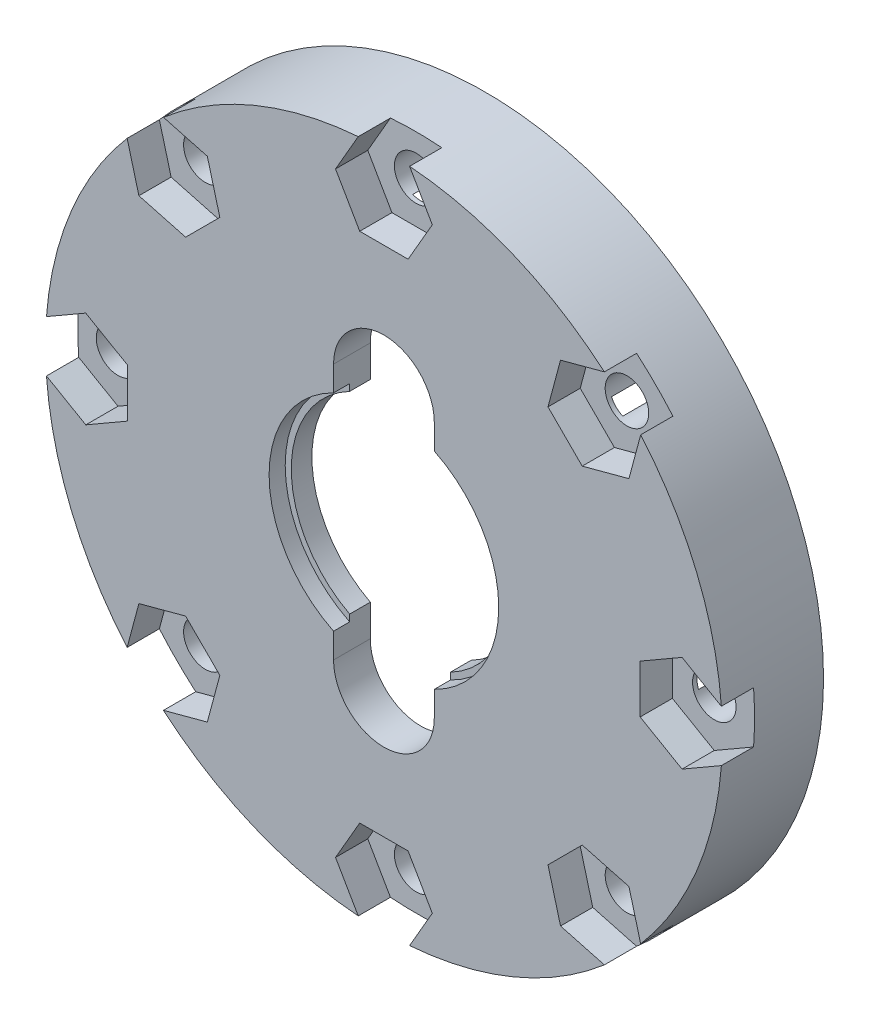
SolidWorks part; units mm, degrees
ref_plane "Front Plane" through (0, 0, 0) normal (0, 0, 1) x (1, 0, 0)
ref_plane "Top Plane" through (0, 0, 0) normal (0, 1, 0) x (1, 0, 0)
ref_plane "Right Plane" through (0, 0, 0) normal (1, 0, 0) x (0, 0, -1)
ref_axis "Z" through (0, 0, -6.594) along (0, 0, 1)
sketch "Sketch3" plane through (0, 0, 0) normal (0, 0, 1) x (1, 0, 0)
  line L0 (-3.125, -6.4031) -> (-3.125, -7.9497)
  line L1 (-3.125, -7.9497) -> (3.125, -7.9497)
  line L2 (3.125, -7.9497) -> (3.125, -6.4031)
  line L3 (3.125, 6.4031) -> (3.125, 7.9494)
  line L4 (3.125, 7.9494) -> (-3.125, 7.9494)
  line L5 (-3.125, 7.9494) -> (-3.125, 6.4031)
  line L132 (3.05, 6.3548) -> (3.05, 6.3561) construction
  line L133 (-3.05, 6.3561) -> (-3.05, 6.3548) construction
  line L134 (3.05, -6.3561) -> (3.05, -6.355) construction
  line L135 (-3.05, -6.355) -> (-3.05, -6.3561) construction
  line L198 (3.05, 6.3548) -> (3.05, 7.8744)
  line L199 (3.05, 7.8744) -> (-3.05, 7.8744)
  line L200 (-3.05, 7.8744) -> (-3.05, 6.3548)
  line L201 (-3.05, 6.3548) -> (-3.4914, 6.1247)
  line L202 (-3.4914, 6.1247) -> (-3.9416, 5.8451)
  line L203 (-3.9416, 5.8451) -> (-4.3696, 5.5325)
  line L204 (-4.3696, 5.5325) -> (-4.7729, 5.1886)
  line L205 (-4.7729, 5.1886) -> (-5.1492, 4.8154)
  line L206 (-5.1492, 4.8154) -> (-5.4964, 4.4149)
  line L207 (-5.4964, 4.4149) -> (-5.8125, 3.9896)
  line L208 (-5.8125, 3.9896) -> (-6.0958, 3.5417)
  line L209 (-6.0958, 3.5417) -> (-6.3446, 3.0737)
  line L210 (-6.3446, 3.0737) -> (-6.5576, 2.5884)
  line L211 (-6.5576, 2.5884) -> (-6.7335, 2.0885)
  line L212 (-6.7335, 2.0885) -> (-6.8714, 1.5768)
  line L213 (-6.8714, 1.5768) -> (-6.9705, 1.0561)
  line L214 (-6.9705, 1.0561) -> (-7.0301, 0.5295)
  line L215 (-7.0301, 0.5295) -> (-7.05, -0.0001)
  line L216 (-7.05, -0.0001) -> (-7.0301, -0.5297)
  line L217 (-7.0301, -0.5297) -> (-6.9705, -1.0563)
  line L218 (-6.9705, -1.0563) -> (-6.8714, -1.577)
  line L219 (-6.8714, -1.577) -> (-6.7335, -2.0887)
  line L220 (-6.7335, -2.0887) -> (-6.5576, -2.5887)
  line L221 (-6.5576, -2.5887) -> (-6.3446, -3.074)
  line L222 (-6.3446, -3.074) -> (-6.0958, -3.5419)
  line L223 (-6.0958, -3.5419) -> (-5.8125, -3.9898)
  line L224 (-5.8125, -3.9898) -> (-5.4964, -4.4152)
  line L225 (-5.4964, -4.4152) -> (-5.1492, -4.8156)
  line L226 (-5.1492, -4.8156) -> (-4.7729, -5.1888)
  line L227 (-4.7729, -5.1888) -> (-4.3696, -5.5327)
  line L228 (-4.3696, -5.5327) -> (-3.9416, -5.8453)
  line L229 (-3.9416, -5.8453) -> (-3.4914, -6.1249)
  line L230 (-3.4914, -6.1249) -> (-3.05, -6.355)
  line L231 (-3.05, -6.355) -> (-3.05, -7.8747)
  line L232 (-3.05, -7.8747) -> (3.05, -7.8747)
  line L233 (3.05, -7.8747) -> (3.05, -6.355)
  line L234 (3.05, -6.355) -> (3.4914, -6.1249)
  line L235 (3.4914, -6.1249) -> (3.9417, -5.8453)
  line L236 (3.9417, -5.8453) -> (4.3696, -5.5327)
  line L237 (4.3696, -5.5327) -> (4.7729, -5.1888)
  line L238 (4.7729, -5.1888) -> (5.1492, -4.8156)
  line L239 (5.1492, -4.8156) -> (5.4964, -4.4152)
  line L240 (5.4964, -4.4152) -> (5.8125, -3.9898)
  line L241 (5.8125, -3.9898) -> (6.0958, -3.5419)
  line L242 (6.0958, -3.5419) -> (6.3447, -3.074)
  line L243 (6.3447, -3.074) -> (6.5576, -2.5887)
  line L244 (6.5576, -2.5887) -> (6.7336, -2.0887)
  line L245 (6.7336, -2.0887) -> (6.8714, -1.577)
  line L246 (6.8714, -1.577) -> (6.9705, -1.0563)
  line L247 (6.9705, -1.0563) -> (7.0301, -0.5297)
  line L248 (7.0301, -0.5297) -> (7.05, -0.0001)
  line L249 (7.05, -0.0001) -> (7.0301, 0.5295)
  line L250 (7.0301, 0.5295) -> (6.9705, 1.0561)
  line L251 (6.9705, 1.0561) -> (6.8714, 1.5768)
  line L252 (6.8714, 1.5768) -> (6.7336, 2.0885)
  line L253 (6.7336, 2.0885) -> (6.5576, 2.5884)
  line L254 (6.5576, 2.5884) -> (6.3447, 3.0737)
  line L255 (6.3447, 3.0737) -> (6.0958, 3.5417)
  line L256 (6.0958, 3.5417) -> (5.8125, 3.9896)
  line L257 (5.8125, 3.9896) -> (5.4964, 4.4149)
  line L258 (5.4964, 4.4149) -> (5.1492, 4.8154)
  line L259 (5.1492, 4.8154) -> (4.7729, 5.1886)
  line L260 (4.7729, 5.1886) -> (4.3696, 5.5325)
  line L261 (4.3696, 5.5325) -> (3.9417, 5.8451)
  line L262 (3.9417, 5.8451) -> (3.4914, 6.1247)
  line L263 (3.4914, 6.1247) -> (3.05, 6.3548)
  line L264 (3.05, 6.3561) -> (3.05, 7.8744) construction
  line L265 (3.05, 7.8744) -> (-3.05, 7.8744) construction
  line L266 (-3.05, 7.8744) -> (-3.05, 6.3561) construction
  line L297 (-3.05, -6.3561) -> (-3.05, -7.8747) construction
  line L298 (-3.05, -7.8747) -> (3.05, -7.8747) construction
  line L299 (3.05, -7.8747) -> (3.05, -6.3561) construction
  arc A1 (-3.05, 6.3561) -> (-3.05, -6.3561) centre (0, 0) ccw construction
  arc A2 (3.05, 6.3561) -> (-3.05, 6.3561) centre (0, 0) ccw construction
  arc A3 (3.05, -6.3561) -> (3.05, 6.3561) centre (0, 0) ccw construction
  arc A4 (-3.05, -6.3561) -> (3.05, -6.3561) centre (0, 0) ccw construction
  circle A5 centre (0, 0) radius 21
  arc A6 (-3.125, 6.4031) -> (-3.125, -6.4031) centre (0, 0) ccw
  arc A7 (3.125, -6.4031) -> (3.125, 6.4031) centre (0, 0) ccw
  dimension "D1" = 14.1
  dimension "D3" = 42
  dimension "D2" = 0.075
  dimension "D4" = 0.075
extrude "Boss-Extrude2" add sketch "Sketch3" against normal blind 1
sketch "Sketch4" plane through (0, 0, -1) normal (0, 0, -1) x (-1, 0, 0)
  line L39 (2.75, 6.1644) -> (2.75, 7.5744)
  line L40 (2.75, 7.5744) -> (-2.75, 7.5744)
  line L41 (-2.75, 7.5744) -> (-2.75, 6.1644)
  line L42 (-2.75, -6.1644) -> (-2.75, -7.5747)
  line L43 (-2.75, -7.5747) -> (2.75, -7.5747)
  line L44 (2.75, -7.5747) -> (2.75, -6.1644)
  circle A14 centre (0, 0) radius 21
  arc A17 (-2.75, 6.1644) -> (-2.75, -6.1644) centre (0, 0) ccw
  arc A18 (2.75, -6.1644) -> (2.75, 6.1644) centre (0, 0) ccw
  dimension "D1" = 42
extrude "Boss-Extrude3" add sketch "Sketch4" along normal blind 5.28
sketch "Sketch5" plane through (0, 0, -6.28) normal (0, 0, -1) x (-1, 0, 0)
  circle A0 centre (0, 0) radius 17.25
  dimension "D1" = 34.5
extrude "Cut-Extrude1" cut sketch "Sketch5" against normal blind 4
sketch "Sketch6" plane through (0, 0, 0) normal (0, 0, 1) x (1, 0, 0)
  line L0 (0, 0) -> (-18.5, 0) construction
  line L1 (-16.3801, 0) -> (0, 0) construction
  line L3 (-21.1, -1.5011) -> (-18.5, -3.0022)
  line L4 (-18.5, -3.0022) -> (-15.9, -1.5011)
  line L5 (-15.9, -1.5011) -> (-15.9, 1.5011)
  line L6 (-15.9, 1.5011) -> (-18.5, 3.0022)
  line L7 (-18.5, 3.0022) -> (-21.1, 1.5011)
  line L8 (-21.1, 1.5011) -> (-21.1, -1.5011)
  circle A0 centre (-18.5, 0) radius 2.6 construction
  dimension "D1" = 0
  dimension "D2" = 18.5
  dimension "D3" = 5.2
extrude "Cut-Extrude2" cut sketch "Sketch6" against normal blind 2
sketch "Sketch8" plane through (0, 0, 0) normal (0, 0, 1) x (1, 0, 0)
  line L0 (36.6653, 0) -> (49.0214, 0) construction
  line L1 (0, 0) -> (-18.5, 0) construction
  circle A0 centre (0, 0) radius 18.5 construction
  circle A1 centre (-18.5, 0) radius 1.35
  dimension "D1" = 37
  dimension "D3" = 2.7
  dimension "D2" = 0
extrude "Cut-Extrude4" cut sketch "Sketch8" against normal through all
pattern_circular "CirPattern1" count 8 over 360 about axis through (0, 0, -6.594) along (0, 0, 1) of "Cut-Extrude2", "Cut-Extrude4"
ref_plane "Plane4" through (0, 0, 0) normal (-0.7071, 0.7071, 0) x (0, 0, 1)
sketch "Sketch9" plane through (0, 0, 0) normal (0, 0, 1) x (1, 0, 0)
  line L1 (-3.125, 7.9494) -> (-3.125, 10.495) construction
  line L2 (0, 0) -> (3.8744, 0) construction
  line L4 (3.125, 7.9494) -> (3.125, -7.9494)
  line L5 (-3.125, 7.9494) -> (-3.125, -7.9494)
  arc A0 (-3.125, 7.9494) -> (3.125, 7.9494) centre (0, 7.9494) cw
  arc A1 (-3.125, -7.9494) -> (3.125, -7.9494) centre (0, -7.9494) ccw
extrude "Cut-Extrude5" cut sketch "Sketch9" against normal through all
equation "\"BearingOD\"= 32"
equation "\"BearingID\" = 25"
equation "\"BearingHeight\"= 4"
equation "\"RetainingRingThickness\" = 1.30"
equation "\"BearingBaseDistance\"= 17.2 - 2*\"BearingHeight\"  - \"RetainingRingThickness\"*2"
equation "\"SeatsOD\"= \"BearingOD\" + 10"
equation "\"WireHarnessHeight\"= 4"
equation "\"OuterWallWidth\"= 6"
equation "\"OverallOD\" = 42"
equation "\"OuterHousingHeight\" = \"WireHarnessHeight\" + \"BearingHeight\"*2 + \"BearingBaseDistance\""
equation "\"RetaininRingGrooveDiameter\" = 23.9"
equation "\"ShaftLengthAfterFlange\" = 2*\"BearingHeight\" + \"BearingBaseDistance\" + \"RetainingRingThickness\"*2\t'give a retaining ring thickness of extra clearance"
equation "\"RetainingRingGrooveBase\" = \"ShaftLengthAfterFlange\" - \"RetainingRingThickness\"*2"
equation "\"CoverThickness\" = 1"
equation "\"CoverClearance\" = 1"
equation "\"FlangHeight\" = 3"
equation "\"PCBWidth\" = 5"
equation "\"PCBHeight\" = \"OuterHousingHeight\" "
equation "\"PCBThickness\" = 1"
equation "\"NormalDistSidewallPCBToZ\" = (\"OverallOD\"/2) - 1.6\t'radial distance from the z axis to pcb origin on the top/connector side"
equation "\"PCBSidewallCutoutClearance\"= 0.1"
equation "\"OutputHubBoltCircleRadius\"= 8"
equation "\"OutputHubOD\"= 27"
equation "\"StatorWireRadius\"= \"NormalDistSidewallPCBToZ\" - 5.7"
equation "\"MountingHoleRadius\"= (\"OverallOD\"+\"BearingOD\")/4"
equation "\"D3@Sketch3\"=\"OverallOD\""
equation "\"D1@Sketch4\"=\"OverallOD\""
equation "\"D1@Sketch8\"=\"MountingHoleRadius\"*2"
equation "\"D2@Sketch6\"=(\"OverallOD\"+\"BearingOD\")/4"
